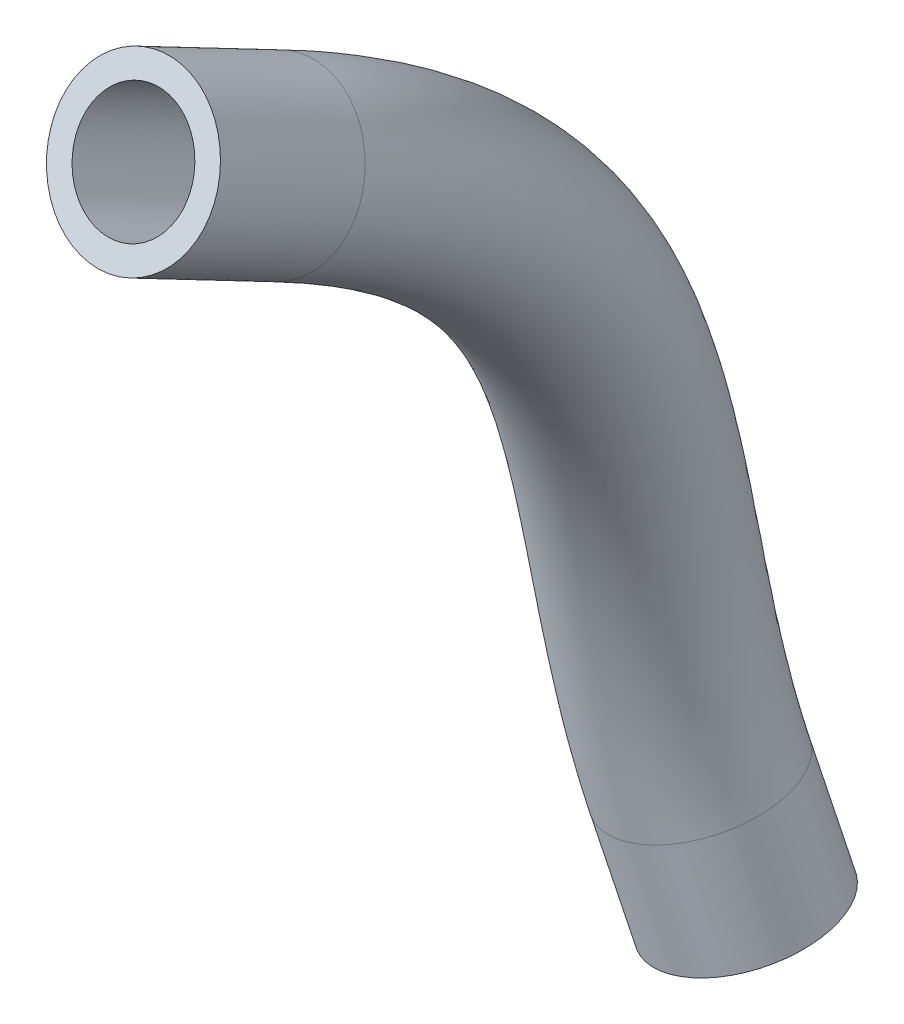
SolidWorks part; units mm, degrees
material "Silicon Rubber"
ref_plane "X-Y Datum" through (0, 0, 0) normal (0, 0, 1) x (1, 0, 0)
ref_plane "X-Z Datum" through (0, 0, 0) normal (0, 1, 0) x (1, 0, 0)
ref_plane "Y-Z Datum" through (0, 0, 0) normal (1, 0, 0) x (0, 0, -1)
sketch3d "3DSketch1"
  line L0 (27.5015, -11.1, -13.9429) -> (23.0956, 7.1738, -10.8516)
  line L1 (25.2459, 131.0659, 60.6955) -> (24.1633, 142.406, 83.3977)
  line L2 (25.2459, 131.0659, 60.6955) -> (24.1633, 142.406, 83.3977) construction
  line L3 (24.1633, 142.406, 83.3977) -> (24.9518, 134.1465, 66.8626) construction
  line L4 (24.1633, 142.406, 83.3977) -> (20.8184, 177.4404, 153.5345) construction
  line L5 (23.0956, 7.1738, -10.8516) -> (24.827, -0.0072, -12.0664) construction
  circle A0 centre (24.9518, 134.1465, 66.8626) radius 9.5 construction
  circle A1 centre (24.1633, 142.406, 83.3977) radius 9.5 construction
  circle A4 centre (24.9518, 134.1465, 66.8626) radius 9.5 construction
  circle A5 centre (24.1633, 142.406, 83.3977) radius 9.5 construction
  circle A14 centre (23.0956, 7.1738, -10.8516) radius 9.525 construction
  circle A15 centre (24.827, -0.0072, -12.0664) radius 9.9344 construction
  circle A16 centre (23.0956, 7.1738, -10.8516) radius 9.525 construction
  circle A17 centre (24.827, -0.0072, -12.0664) radius 9.9344 construction
  spline S0 degree 3 poles (23.0956, 7.1738, -10.8516) (13.2611, 47.9635, -3.9512) (28.1777, 100.3585, -0.7791) (25.2459, 131.0659, 60.6955) knots 0 0 0 0 1 1 1 1
  point P8 (24.5469, 138.3879, 75.3536)
  point P11 (23.7583, 146.6474, 91.8887)
  point P13 (24.5469, 138.3879, 75.3536)
  point P15 (20.8927, 16.3108, -9.3059)
  point P19 (22.5294, 9.5224, -10.4543)
  point P21 (20.8927, 16.3108, -9.3059)
  point P24 (22.5294, 9.5224, -10.4543)
  point P26 (23.7583, 146.6474, 91.8887)
  dimension "D2" = 19.05
  dimension "D1" = 25.4
sweep "Sweep1" add path "3DSketch1" circular profile diameter 26.9875 parameters "D3"=26.9875
sweep "Cut-Sweep1" cut path "3DSketch1<2>" circular profile diameter 19.05 parameters "D3"=19.05
sketch3d "3DSketch1<2>" same geometry as "3DSketch1"
